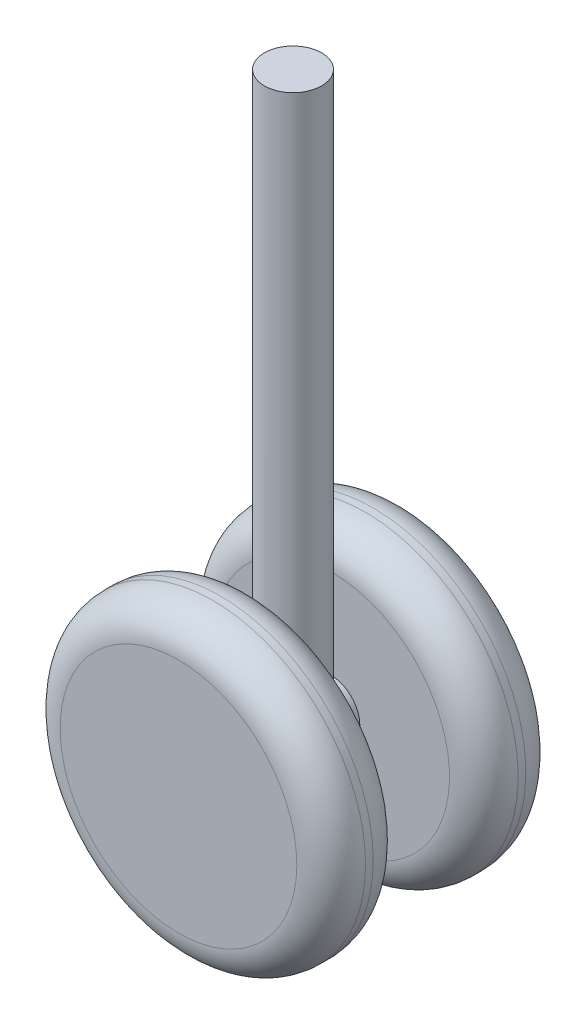
SolidWorks part; units mm, degrees
ref_plane "Plano frontal" through (0, 0, 0) normal (0, 0, 1) x (1, 0, 0)
ref_plane "Plano superior" through (0, 0, 0) normal (0, 1, 0) x (1, 0, 0)
ref_plane "Plano direito" through (0, 0, 0) normal (1, 0, 0) x (0, 0, -1)
sketch "Esboço1" plane through (0, 0, 0) normal (0, 1, 0) x (1, 0, 0)
  circle A0 centre (0, 0) radius 75
  dimension "D1" = 150
extrude "Ressalto-extrusão1" add sketch "Esboço1" along normal blind 1500
sketch "Esboço2" plane through (0, 0, 0) normal (0, 0, 1) x (1, 0, 0)
  circle A0 centre (0, 0) radius 75
extrude "Ressalto-extrusão2" add sketch "Esboço2" along normal blind 200 and the other way blind 200
ref_plane "Plano1" through (0, 0, 200) normal (0, 0, 1) x (1, 0, 0)
sketch "Esboço3" plane through (0, 0, 200) normal (0, 0, 1) x (1, 0, 0)
  circle A0 centre (0, 0) radius 400
  dimension "D1" = 800
extrude "Ressalto-extrusão3" add sketch "Esboço3" along normal blind 100 and the other way blind 100
fillet "Filete1" radius 90 2 edges at (400, 0, 300) (400, 0, 100)
mirror "Espelhar1" about plane through (0, 0, 0) normal (0, 0, 1) of "Ressalto-extrusão3", "Filete1"
